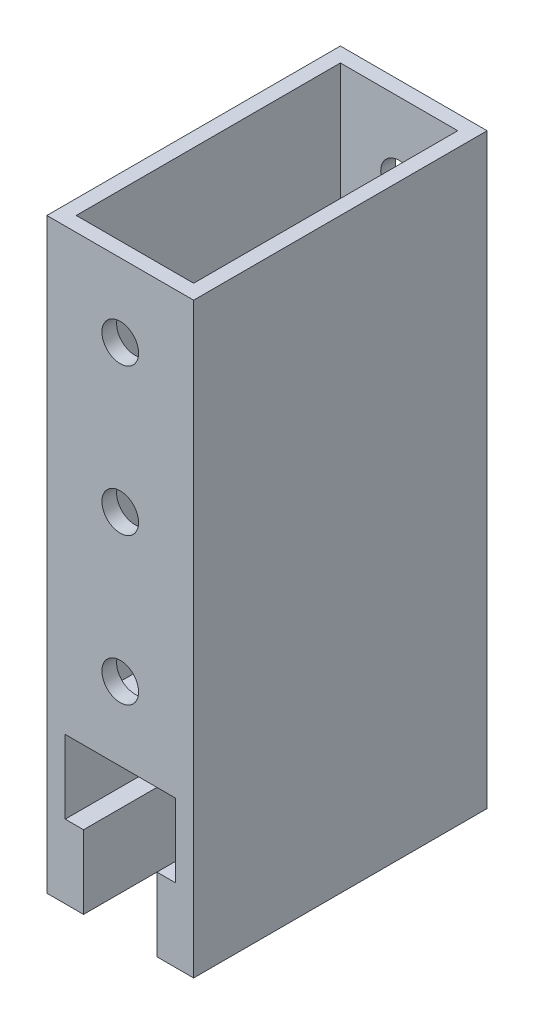
SolidWorks part; units mm, degrees
ref_plane "Front Plane" through (0, 0, 0) normal (0, 0, 1) x (1, 0, 0)
ref_plane "Top Plane" through (0, 0, 0) normal (0, 1, 0) x (1, 0, 0)
ref_plane "Right Plane" through (0, 0, 0) normal (1, 0, 0) x (0, 0, -1)
sketch "Sketch1" plane through (0, 0, 0) normal (0, 0, 1) x (1, 0, 0)
  line L1 (0, 0) -> (25.4, 0)
  line L2 (0, 0) -> (0, 101.6)
  line L3 (0, 101.6) -> (25.4, 101.6)
  line L4 (25.4, 0) -> (25.4, 101.6)
  dimension "D1" = 101.6
  dimension "D2" = 25.4
extrude "Boss-Extrude1" add sketch "Sketch1" along normal mid plane 50.8
sketch "Sketch2" plane through (0, 0, 25.4) normal (0, 0, 1) x (1, 0, 0)
  circle A1 centre (12.7, 38.1) radius 3.175
  circle A2 centre (12.7, 63.5) radius 3.175
  circle A3 centre (12.7, 88.9) radius 3.175
  dimension "D2" = 6.35
  dimension "D3" = 6.35
  dimension "D4" = 6.35
  dimension "D7" = 25.4
  dimension "D8" = 25.4
extrude "Cut-Extrude1" cut sketch "Sketch2" against normal through all
sketch "Sketch3" plane through (0, 101.6, 0) normal (0, 1, 0) x (1, 0, 0)
  line L0 (0, -25.4) -> (0, 25.4) construction
  line L1 (2.54, -22.86) -> (22.86, -22.86)
  line L2 (2.54, -22.86) -> (2.54, 22.86)
  line L3 (2.54, 22.86) -> (22.86, 22.86)
  line L4 (22.86, -22.86) -> (22.86, 22.86)
  line L5 (25.4, -25.4) -> (0, -25.4) construction
  dimension "D1" = 20.32
  dimension "D2" = 45.72
  dimension "D3" = 2.54
  dimension "D4" = 2.54
extrude "Cut-Extrude2" cut sketch "Sketch3" against normal blind 73.66
sketch "Sketch5" plane through (0, 0, 25.4) normal (0, 0, 1) x (1, 0, 0)
  line L0 (6.35, 0) -> (6.35, 12.7)
  line L2 (6.35, 12.7) -> (3.175, 12.7)
  line L3 (3.175, 12.7) -> (3.175, 25.4)
  line L4 (3.175, 25.4) -> (22.225, 25.4)
  line L5 (22.225, 25.4) -> (22.225, 12.7)
  line L6 (22.225, 12.7) -> (19.05, 12.7)
  line L7 (19.05, 12.7) -> (19.05, 0)
  line L8 (19.05, 0) -> (6.35, 0)
  line L9 (0, 0) -> (25.4, 0) construction
  dimension "D1" = 12.7
  dimension "D2" = 12.7
  dimension "D3" = 12.7
  dimension "D4" = 12.7
  dimension "D5" = 0
extrude "Cut-Extrude4" cut sketch "Sketch5" against normal through all
